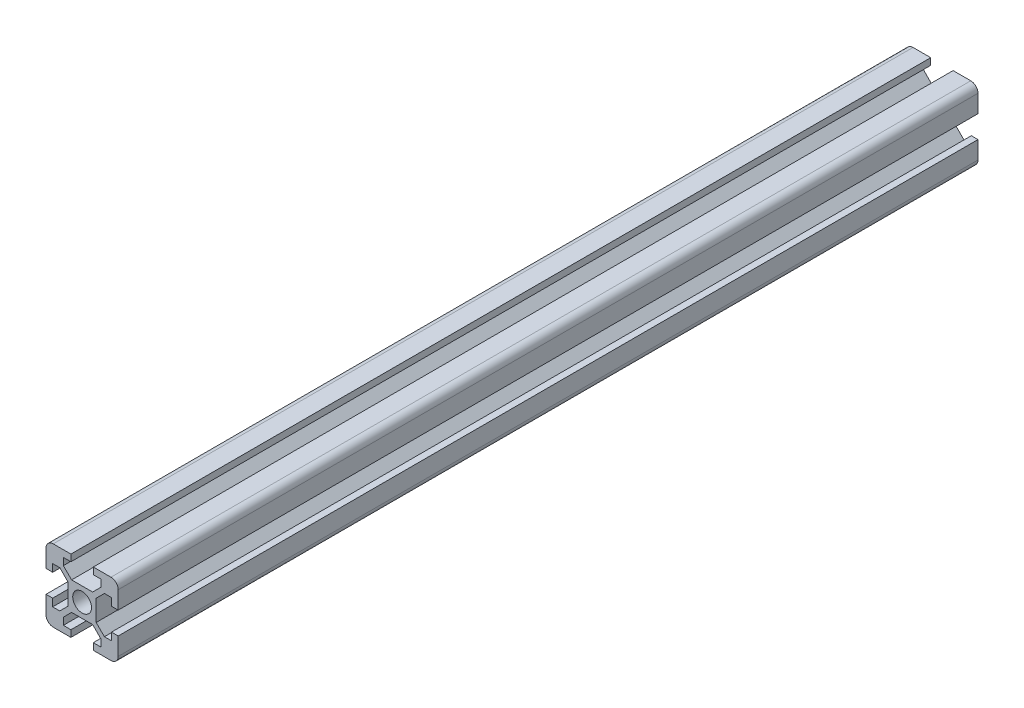
SolidWorks part; units mm, degrees
ref_plane "Front Plane" through (0, 0, 0) normal (0, 0, 1) x (1, 0, 0)
ref_plane "Top Plane" through (0, 0, 0) normal (0, 1, 0) x (1, 0, 0)
ref_plane "Right Plane" through (0, 0, 0) normal (1, 0, 0) x (0, 0, -1)
sketch "Sketch1" plane through (0, 0, 0) normal (0, 0, 1) x (1, 0, 0)
  line L1 (-3.9, 2.9101) -> (-6.1799, 5.19)
  line L2 (-8.15, 5.19) -> (-8.15, 3.1)
  line L3 (-8.15, 3.1) -> (-10, 3.1)
  line L4 (-10, 3.1) -> (-10, 10)
  line L5 (-10, 10) -> (-3.1, 10)
  line L6 (-3.1, 10) -> (-3.1, 8.15)
  line L7 (-3.1, 8.15) -> (-5.19, 8.15)
  line L8 (-5.19, 6.1799) -> (-2.9101, 3.9)
  line L10 (0, 15.4917) -> (0, -11.1126) construction
  line L11 (-16.3459, 0) -> (7.5931, 0) construction
  line L21 (16.3459, 0) -> (-7.5931, 0) construction
  line L39 (-8.15, 5.19) -> (-6.1799, 5.19)
  line L40 (-5.19, 6.1799) -> (-5.19, 8.15)
  line L41 (-3.9, 2.9101) -> (-3.9, -2.9101)
  line L42 (-2.9101, 3.9) -> (2.9101, 3.9)
  line L43 (-2.9101, -3.9) -> (2.9101, -3.9)
  line L44 (-5.19, -6.1799) -> (-5.19, -8.15)
  line L45 (-8.15, -5.19) -> (-6.1799, -5.19)
  line L46 (-5.19, -6.1799) -> (-2.9101, -3.9)
  line L47 (-3.1, -8.15) -> (-5.19, -8.15)
  line L48 (-3.1, -10) -> (-3.1, -8.15)
  line L49 (-10, -10) -> (-3.1, -10)
  line L50 (-10, -3.1) -> (-10, -10)
  line L51 (-8.15, -3.1) -> (-10, -3.1)
  line L52 (-8.15, -5.19) -> (-8.15, -3.1)
  line L53 (-3.9, -2.9101) -> (-6.1799, -5.19)
  line L54 (-16.3459, 0) -> (7.5931, 0) construction
  line L55 (3.9, -2.9101) -> (6.1799, -5.19)
  line L56 (8.15, -5.19) -> (8.15, -3.1)
  line L57 (8.15, -3.1) -> (10, -3.1)
  line L58 (10, -3.1) -> (10, -10)
  line L59 (10, -10) -> (3.1, -10)
  line L60 (3.1, -10) -> (3.1, -8.15)
  line L61 (3.1, -8.15) -> (5.19, -8.15)
  line L62 (5.19, -6.1799) -> (2.9101, -3.9)
  line L63 (8.15, -5.19) -> (6.1799, -5.19)
  line L64 (5.19, -6.1799) -> (5.19, -8.15)
  line L65 (3.9, 2.9101) -> (3.9, -2.9101)
  line L66 (5.19, 6.1799) -> (5.19, 8.15)
  line L67 (8.15, 5.19) -> (6.1799, 5.19)
  line L68 (5.19, 6.1799) -> (2.9101, 3.9)
  line L69 (3.1, 8.15) -> (5.19, 8.15)
  line L70 (3.1, 10) -> (3.1, 8.15)
  line L71 (10, 10) -> (3.1, 10)
  line L72 (10, 3.1) -> (10, 10)
  line L73 (8.15, 3.1) -> (10, 3.1)
  line L74 (8.15, 5.19) -> (8.15, 3.1)
  line L75 (3.9, 2.9101) -> (6.1799, 5.19)
  circle A0 centre (0, 0) radius 2.6
  point P19 (-3.9, 0)
  point P20 (-3.9, 0)
  point P37 (0, -3.9)
  point P38 (0, 3.9)
  point P46 (3.9, 0)
  point P50 (0, -3.9)
  point P53 (0, 3.9)
  dimension "D8" = 5.2
  dimension "D1" = 10
  dimension "D2" = 10
  dimension "D3" = 6.1
  dimension "D4" = 1.4
  dimension "D5" = 6.1
  dimension "D6" = 1.85
  dimension "D7" = 6.9
  dimension "D9" = 4.81
  dimension "D10" = 4.81
extrude "Boss-Extrude1" add sketch "Sketch1" against normal blind 238.202
fillet "Fillet1" radius 2 4 edges at (10, -10, -119.101) (-10, -10, -119.101) (10, 10, -119.101) (-10, 10, -119.101)
